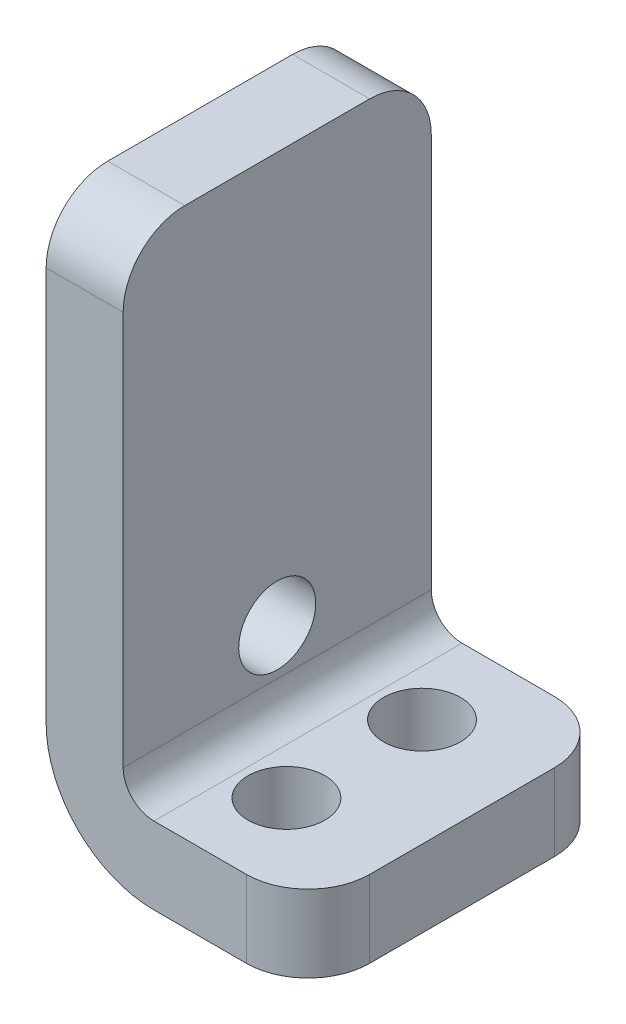
SolidWorks part; units mm, degrees
material "6061 Alloy"
ref_plane "Front Plane" through (0, 0, 0) normal (0, 0, 1) x (1, 0, 0)
ref_plane "Top Plane" through (0, 0, 0) normal (0, 1, 0) x (1, 0, 0)
ref_plane "Right Plane" through (0, 0, 0) normal (1, 0, 0) x (0, 0, -1)
sketch "Sketch1" plane through (0, 0, 0) normal (0, 0, 1) x (1, 0, 0)
  line L0 (0, 31.7868) -> (0, 12.9908)
  line L1 (1.27, 11.7208) -> (7.62, 11.7208)
  line L2 (-3.175, 31.7868) -> (-3.175, 12.9908)
  line L3 (1.27, 8.5458) -> (7.62, 8.5458)
  line L4 (-3.175, 31.7868) -> (0, 31.7868)
  line L5 (7.62, 11.7208) -> (7.62, 8.5458)
  arc A0 (1.27, 11.7208) -> (0, 12.9908) centre (1.27, 12.9908) cw
  arc A1 (1.27, 8.5458) -> (-3.175, 12.9908) centre (1.27, 12.9908) cw
  dimension "D1" = 1.27
  dimension "D2" = 6.35
  dimension "D3" = 18.796
  dimension "D4" = 3.175
extrude "Boss-Extrude1" add sketch "Sketch1" along normal blind 12.7
fillet "Fillet1" radius 2.54 4 edges at (7.62, 10.1333, 12.7) (7.62, 10.1333, 0) (-1.5875, 31.7868, 12.7) (-1.5875, 31.7868, 0)
sketch "Sketch3" plane through (0, 11.7208, 0) normal (0, 1, 0) x (1, 0, 0)
  line L0 (3.175, -12.7) -> (3.175, 0)
  line L1 (5.08, -12.7) -> (1.27, -12.7) construction
  line L2 (5.08, 0) -> (1.27, 0) construction
  circle A0 centre (3.175, -9.144) radius 1.5875
  circle A1 centre (3.175, -3.556) radius 1.5875
  dimension "D1" = 3.556
  dimension "D3" = 3.175
  dimension "D4" = 3.175
  dimension "D2" = 3.556
extrude "Cut-Extrude2" cut sketch "Sketch3" against normal up to next contours L0 A0 | L0 A0 | L0 A1 | L0 A1 region at (2.5012, 11.7208, 9.144) region at (2.5012, 11.7208, 3.556) region at (3.8488, 11.7208, 3.556) region at (3.8488, 11.7208, 9.144)
sketch "Sketch4" plane through (0, 8.5458, 0) normal (0, -1, 0) x (1, 0, 0)
  line L0 (1.27, 6.35) -> (7.62, 6.35)
  line L1 (1.27, 12.7) -> (1.27, 0) construction
  line L2 (7.62, 10.16) -> (7.62, 2.54) construction
sketch "Sketch5" plane through (0, 0, 0) normal (1, 0, 0) x (0, 0, -1)
  line L0 (-12.7, 8.5458) -> (0, 8.5458) construction
  line L1 (-6.35, 12.9908) -> (-6.35, 18.2092) construction
  line L4 (-2.54, 31.7868) -> (-10.16, 31.7868)
  line L5 (-12.7, 29.2468) -> (-12.7, 12.9908)
  line L6 (-12.7, 12.9908) -> (0, 12.9908)
  line L7 (0, 12.9908) -> (0, 29.2468)
  line L8 (-2.54, 31.7868) -> (-10.16, 31.7868)
  line L9 (-12.7, 29.2468) -> (-12.7, 12.9908)
  line L10 (-12.7, 12.9908) -> (0, 12.9908)
  line L11 (0, 12.9908) -> (0, 29.2468)
  circle A1 centre (-6.35, 14.8958) radius 1.5875
  arc A2 (-10.16, 31.7868) -> (-12.7, 29.2468) centre (-10.16, 29.2468) ccw
  arc A3 (0, 29.2468) -> (-2.54, 31.7868) centre (-2.54, 29.2468) ccw
  arc A4 (-10.16, 31.7868) -> (-12.7, 29.2468) centre (-10.16, 29.2468) ccw
  arc A5 (0, 29.2468) -> (-2.54, 31.7868) centre (-2.54, 29.2468) ccw
  point P2 (0, 0)
  dimension "D2" = 6.35
  dimension "D1" = 0
extrude "Cut-Extrude3" cut sketch "Sketch5" against normal up to next contours L1 A1 | A1 L1 region at (0, 14.8958, 7.0238) region at (0, 14.8958, 5.6762)
